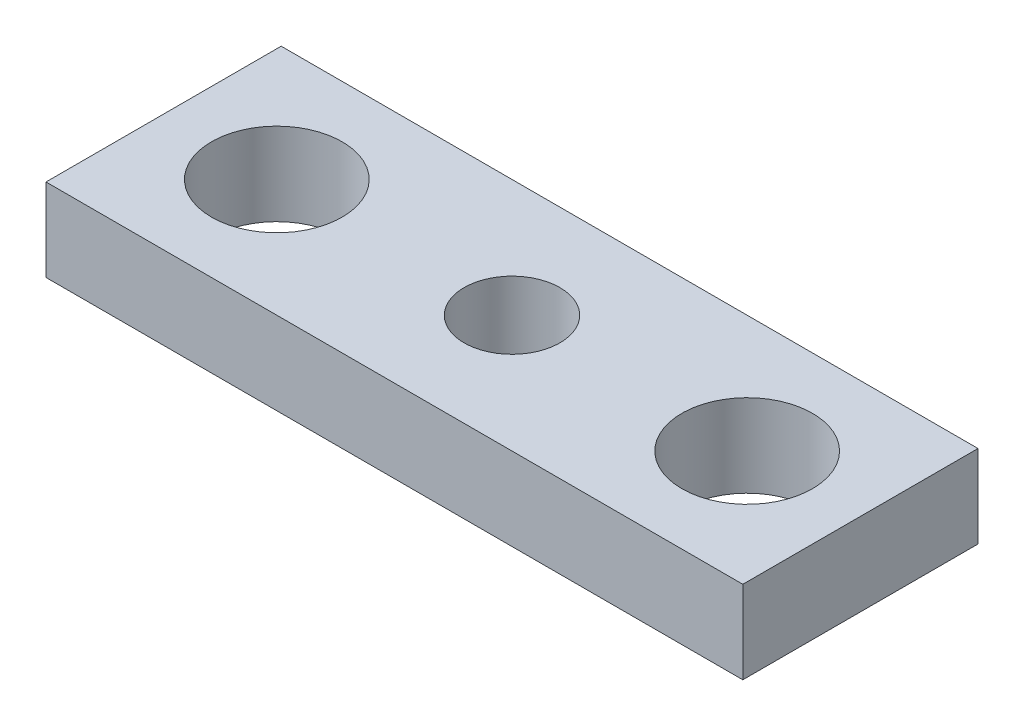
SolidWorks part; units mm, degrees
ref_plane "前视基准面" through (0, 0, 0) normal (0, 0, 1) x (1, 0, 0)
ref_plane "上视基准面" through (0, 0, 0) normal (0, 1, 0) x (1, 0, 0)
ref_plane "右视基准面" through (0, 0, 0) normal (1, 0, 0) x (0, 0, -1)
sketch "草图1" plane through (0, 0, 0) normal (0, 1, 0) x (1, 0, 0)
  line L1 (-40, 13.5) -> (40, 13.5)
  line L2 (-40, 13.5) -> (-40, -13.5)
  line L3 (-40, -13.5) -> (40, -13.5)
  line L4 (40, 13.5) -> (40, -13.5)
  line L5 (-40, 13.5) -> (40, -13.5) construction
  line L6 (-40, -13.5) -> (40, 13.5) construction
  point P0 (0, 0)
  dimension "D1" = 80
  dimension "D2" = 27
extrude "凸台-拉伸1" add sketch "草图1" along normal blind 9.5
sketch "草图2" plane through (0, 0, 0) normal (0, -1, 0) x (1, 0, 0)
  line L0 (-40, 0) -> (40, 0) construction
  line L1 (-40, -13.5) -> (-40, 13.5) construction
  line L2 (40, 13.5) -> (40, -13.5) construction
ref_plane "基准面1" through (0, 0, 0) normal (0, 0, 1) x (1, 0, 0)
sketch "草图3" plane through (0, 9.5, 0) normal (0, 1, 0) x (1, 0, 0)
  line L0 (-14.85, 0) -> (14.85, 0) construction
  line L1 (0, 13.5) -> (0, -13.5) construction
  line L2 (40, 13.5) -> (-40, 13.5) construction
  line L3 (-40, -13.5) -> (40, -13.5) construction
  circle A0 centre (-27, 0) radius 7.5
  circle A1 centre (27, 0) radius 7.5
  dimension "D1" = 15
  dimension "D2" = 54
extrude "切除-拉伸1" cut sketch "草图3" against normal through all contours A1 | A0
sketch "草图7" plane through (-40, 0, 0) normal (-1, 0, 0) x (0, 0, 1)
  line L0 (-13.5, 4.75) -> (13.5, 4.75) construction
  line L1 (-13.5, 9.5) -> (-13.5, 0) construction
  line L2 (13.5, 9.5) -> (13.5, 0) construction
ref_plane "基准面3" through (0, 4.75, 0) normal (0, 1, 0) x (1, 0, 0)
sketch "草图9" plane through (0, 4.75, 0) normal (0, 1, 0) x (1, 0, 0)
  line L0 (-44.1863, 9.5) -> (43.8901, 9.5) construction
  line L1 (40, 13.5) -> (-40, 13.5) construction
  line L2 (-40, -9.5) -> (39.6508, -9.5) construction
  line L3 (-40, 13.5) -> (-40, -13.5) construction
  line L4 (-40, -13.5) -> (40, -13.5) construction
  dimension "D1" = 4
  dimension "D2" = 4
sketch "草图10" plane through (0, 0, 0) normal (0, -1, 0) x (1, 0, 0)
  circle A1 centre (0, 0) radius 5.5
  dimension "D1" = 11
extrude "切除-拉伸2" cut sketch "草图10" against normal through all
